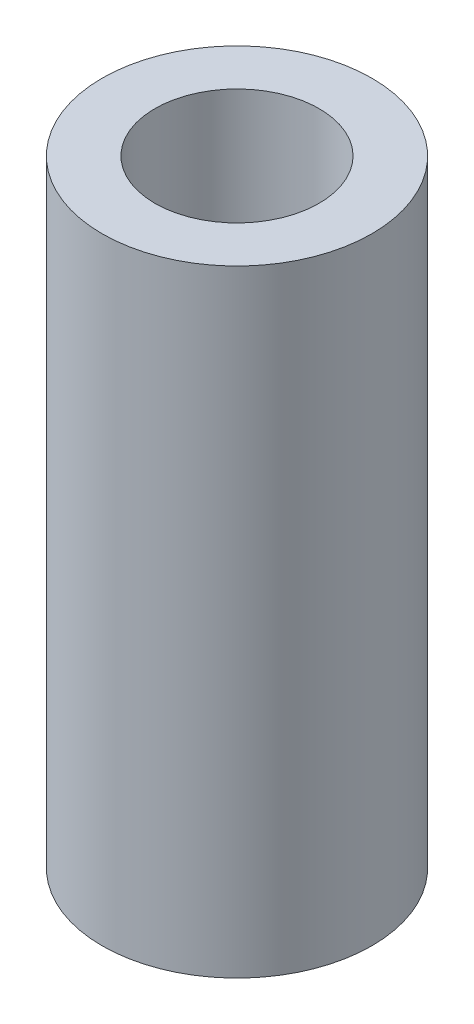
SolidWorks part; units mm, degrees
ref_plane "Front Plane" through (0, 0, 0) normal (0, 0, 1) x (1, 0, 0)
ref_plane "Top Plane" through (0, 0, 0) normal (0, 1, 0) x (1, 0, 0)
ref_plane "Right Plane" through (0, 0, 0) normal (1, 0, 0) x (0, 0, -1)
sketch "Sketch1" plane through (0, 0, 0) normal (0, 1, 0) x (1, 0, 0)
  circle A0 centre (0, 0) radius 12.5
  dimension "SLEEVE_OD" = 25
extrude "Boss-Extrude1" add sketch "Sketch1" along normal blind 57.1769
sketch "Sketch2" plane through (0, 0, 0) normal (0, 1, 0) x (1, 0, 0)
  circle A0 centre (0, 0) radius 7.6113
  dimension "BORE_D" = 15.2226
extrude "Cut-Extrude1" cut sketch "Sketch2" along normal through all
chamfer "Chamfer1" distance 2.429 angle 60 rebuild error yes
